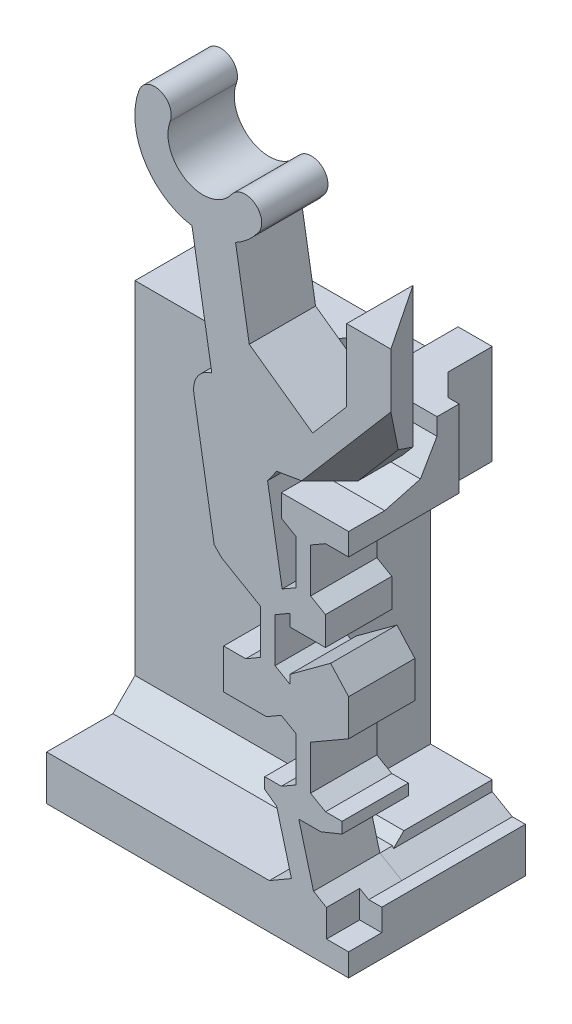
SolidWorks part; units mm, degrees
material "Nylon 6/12"
ref_plane "Front Plane" through (0, 0, 0) normal (0, 0, 1) x (1, 0, 0)
ref_plane "Top Plane" through (0, 0, 0) normal (0, 1, 0) x (1, 0, 0)
ref_plane "Right Plane" through (0, 0, 0) normal (1, 0, 0) x (0, 0, -1)
sketch "Sketch-SkeletonConfigUp" plane through (0, 0, 0) normal (0, 0, 1) x (1, 0, 0)
  line L0 (0, 0) -> (0, -50000) construction
  line L1 (0, 0) -> (4.5811, 6.2164) construction
  line L2 (9.8143, 13.3177) -> (4.5811, 13.945) construction
  line L3 (4.5811, 13.945) -> (2.9713, 10.4094) construction
  line L4 (2.9713, 10.4094) -> (4.5811, 6.2164) construction
  line L5 (4.5811, 13.945) -> (6.2429, 19.1409) construction
  line L6 (2.9713, 10.4094) -> (0.0405, 27.8193) construction
  line L7 (4.5811, 6.2164) -> (9.8143, 13.3177) construction
  line L8 (-587.3593, -797.0242) -> (9.8143, 13.3177) construction
  dimension "D2" = 7.7221
  dimension "D3" = 8.8212
  dimension "D4" = 5.2707
  dimension "D5" = 119.553
  dimension "D6" = 3.8848
  dimension "D7" = 5.4552
  dimension "D8" = 17.6549
  dimension "D9" = 4.4914
  dimension "D10" = 6.745
  dimension "D11" = 145.964
  dimension "D12" = 143.612
sketch "Sketch-SkeletonConfigDown" plane through (0, 0, 0) normal (0, 0, 1) x (1, 0, 0)
  line L0 (0, 0) -> (0, -50000) construction
  line L1 (0, 0) -> (4.5811, 6.2164) construction
  line L2 (9.8143, 13.3177) -> (4.5811, 13.945) construction
  line L3 (4.5811, 13.945) -> (6.1909, 10.4094) construction
  line L4 (6.1909, 10.4094) -> (4.5811, 6.2164) construction
  line L5 (4.5811, 13.945) -> (1.753, 18.6098) construction
  line L6 (6.1909, 10.4094) -> (-8.8652, 19.6294) construction
  line L7 (4.5811, 6.2164) -> (9.8143, 13.3177) construction
  line L8 (-589.9357, -800.5203) -> (9.8143, 13.3177) construction
  dimension "D2" = 7.7221
  dimension "D3" = 8.8212
  dimension "D4" = 5.2707
  dimension "D5" = 119.553
  dimension "D6" = 3.8848
  dimension "D7" = 5.4552
  dimension "D8" = 17.6549
  dimension "D9" = 4.4914
  dimension "D10" = 6.745
  dimension "D11" = 145.964
  dimension "D1" = 143.612
ref_plane "Plane-Cam Base" through (9.128, 0, 0) normal (1, 0, 0) x (0, 0, -1)
ref_plane "Plane-Down-to-Up Derailleur Clearance" through (6.628, 0, 0) normal (1, 0, 0) x (0, 0, -1)
ref_plane "Plane-Cam Cavity Roof" through (5.128, 0, 0) normal (1, 0, 0) x (0, 0, -1)
sketch "Sketch-SwitchBossUp" plane through (0, 0, 0) normal (0, 0, 1) x (1, 0, 0)
  line L0 (3.5811, 11.4759) -> (3.5811, 12.945) construction
  line L2 (6.5405, 21.1774) -> (6.5405, 24.4384)
  line L3 (6.5405, 24.4384) -> (8.5405, 24.4384)
  line L4 (8.5405, 24.4384) -> (8.5405, 20.4384)
  line L5 (5.5811, 12.5552) -> (5.5811, 11.263)
  line L7 (1.5115, 25.1048) -> (2.5464, 18.9575)
  line L8 (-0.4607, 24.7728) -> (0.4359, 19.4465)
  line L9 (2.9713, 10.4094) -> (0.0405, 27.8193) construction
  line L11 (-0.0396, 22.2712) -> (1.9326, 22.6032) construction
  line L15 (6.628, -23.7286) -> (6.628, 23.7286) construction
  line L16 (2.9713, 10.4094) -> (4.5811, 6.2164) construction
  line L17 (3.5811, 12.945) -> (3.5811, 14.945) construction
  line L18 (5.5811, 12.945) -> (5.5811, 14.945) construction
  line L19 (4.2561, 13.945) -> (4.9061, 13.945) construction
  line L20 (3.5811, 14.945) -> (5.5811, 14.945) construction
  line L21 (3.5811, 12.945) -> (5.5811, 12.945) construction
  line L22 (4.5811, 12.945) -> (4.5811, 14.945) construction
  line L23 (4.5811, 6.2164) -> (8.5405, 7.1023) construction
  line L24 (1.9713, 9.4094) -> (1.9713, 11.4094) construction
  line L25 (3.9713, 9.4094) -> (3.9713, 11.4094) construction
  line L26 (3.9713, 9.4094) -> (1.9713, 9.4094) construction
  line L27 (1.9713, 11.4094) -> (3.9713, 11.4094) construction
  line L28 (3.5811, 7.2164) -> (5.5811, 7.2164) construction
  line L29 (3.5811, 7.2164) -> (3.5811, 5.2164) construction
  line L30 (5.5811, 7.2164) -> (5.5811, 5.2164) construction
  line L31 (3.5811, 5.2164) -> (5.5811, 5.2164) construction
  line L32 (4.9061, 6.2164) -> (4.2561, 6.2164) construction
  line L40 (3.2963, 10.4094) -> (2.6463, 10.4094) construction
  line L43 (2.874, 4.5093) -> (0.7934, 4.5093) construction
  line L51 (4.9929, 19.3693) -> (2.5464, 18.9575)
  line L66 (0.0405, 27.8193) -> (0.0405, 50027.8193) construction
  line L74 (0.5455, 12.7717) -> (-0.3728, 18.2264)
  line L75 (0.3841, 13.7302) -> (2.3564, 14.0622) construction
  line L76 (5.5811, 11.263) -> (5.5811, 12.5552) construction
  line L77 (5.5811, 7.6061) -> (6.628, 8.2105)
  line L80 (5.8152, 10.763) -> (6.628, 9.8603)
  line L81 (8.5405, 1033.6218) -> (8.5405, 20.4384) construction
  line L82 (2.5464, 18.9575) -> (3.5585, 12.945) construction
  line L83 (3.6203, 12.5779) -> (2.8784, 16.9852)
  line L84 (2.8784, 16.9852) -> (6.0405, 17.5175)
  line L85 (6.9307, 9.5241) -> (8.5405, 7.7363) construction
  line L88 (3.5811, 16.3347) -> (6.8573, 16.3347)
  line L92 (3.7762, 8.3129) -> (6.9307, 9.5241) construction
  line L93 (6.3311, 4.3267) -> (5.3731, 3.937)
  line L95 (2.5464, 18.9575) -> (2.8784, 16.9852) construction
  line L96 (2.7124, 17.9713) -> (8.5405, 18.9524) construction
  line L97 (2.7124, 17.9713) -> (1.7262, 17.8053) construction
  line L98 (1.9713, 9.0197) -> (0.9713, 9.0197)
  line L99 (0.9713, 9.0197) -> (0.9713, 7.2164)
  line L100 (0.9713, 7.2164) -> (2.9061, 7.2164)
  line L101 (4.5811, 6.2164) -> (6.9307, 9.5241) construction
  line L103 (0.0405, 27.8193) -> (1.9448, 26.4638) construction
  line L104 (6.9307, 9.5241) -> (8.5405, 7.7363) construction
  line L106 (13.4511, 14.945) -> (5.5811, 14.945) construction
  line L107 (1.9713, 9.4094) -> (1.9713, 9.0197) construction
  line L109 (0.0405, 27.8193) -> (-2.1498, 28.6358) construction
  line L110 (8.5405, 20.4384) -> (6.0405, 17.5175)
  line L111 (6.628, 9.8603) -> (6.628, 8.2105)
  line L112 (6.628, 9.8603) -> (6.9307, 9.5241) construction
  line L113 (2.8311, 4.8267) -> (2.8311, 4.3267)
  line L114 (7.3693, 7.7363) -> (7.3563, 7.7363) construction
  line L115 (6.8573, 16.3347) -> (13.4511, 16.3347)
  line L116 (13.4511, 16.3347) -> (13.4511, -1.1653)
  line L117 (13.4511, -1.1653) -> (5.0405, -1.1653)
  line L119 (10.4375, 14.0252) -> (10.4375, 2.1692)
  line L121 (5.0405, -1.1653) -> (5.0405, 1.4417) construction
  line L122 (8.237, 12.8031) -> (10.844, 12.8031) construction
  line L123 (10.844, 12.8031) -> (13.4511, 12.8031) construction
  line L124 (10.4375, 2.1692) -> (9.128, 0.8597)
  line L125 (8.5405, 7.5847) -> (13.4511, 7.5847) construction
  line L127 (5.5811, 15.3347) -> (5.5811, 14.945) construction
  line L130 (6.0377, 0.8597) -> (9.128, 0.8597)
  line L132 (2.8311, 4.3267) -> (3.3706, 3.937)
  line L133 (2.9713, 10.4094) -> (6.1909, 10.4094) construction
  line L134 (4.5811, 10.4094) -> (4.5811, 13.945) construction
  line L135 (4.5811, 10.4094) -> (4.5811, 6.2164) construction
  line L136 (0.8973, 12.4192) -> (0.5455, 12.7717)
  line L137 (3.9713, 9.4094) -> (5.5811, 7.2164) construction
  line L139 (5.8152, 10.763) -> (3.9713, 9.4094)
  line L141 (4.0405, 1.437) -> (3.0405, 0.8597)
  line L142 (3.0405, 0.8597) -> (3.0405, -1.1653)
  line L143 (8.5405, 20.4384) -> (8.5405, 18.9524) construction
  line L145 (8.5405, 17.9384) -> (8.5405, -49992.0368) construction
  line L147 (5.5811, 11.263) -> (5.5811, 12.5552) construction
  line L149 (6.3311, 4.8267) -> (6.3311, 4.3267)
  line L150 (3.0405, -1.1653) -> (5.0405, -1.1653)
  line L151 (3.3706, 3.937) -> (5.3731, 3.937) construction
  line L152 (4.2561, 14.945) -> (4.2561, 12.945)
  line L153 (4.9061, 14.945) -> (4.9061, 12.945)
  line L155 (4.2561, 14.945) -> (3.5811, 15.3347)
  line L156 (4.9061, 14.945) -> (5.5811, 15.3347)
  line L157 (3.5811, 16.3347) -> (3.5811, 15.3347)
  line L158 (5.5811, 15.3347) -> (9.128, 15.3347)
  line L162 (3.2963, 11.4094) -> (3.2963, 9.4094)
  line L164 (2.6463, 11.4094) -> (2.6463, 9.4094)
  line L169 (4.2561, 7.2164) -> (4.2561, 5.2164)
  line L170 (4.9061, 5.2164) -> (4.9061, 7.2164)
  line L175 (4.2561, 7.2164) -> (3.5811, 7.6061)
  line L176 (4.9061, 7.2164) -> (5.5811, 7.6061)
  line L177 (5.5811, 7.2164) -> (5.5811, 7.6061) construction
  line L179 (4.2561, 5.2164) -> (3.5811, 4.8267)
  line L180 (3.5811, 5.2164) -> (3.5811, 4.8267) construction
  line L181 (3.5811, 4.8267) -> (2.8311, 4.8267)
  line L183 (4.9061, 5.2164) -> (5.5811, 4.8267)
  line L184 (5.5811, 5.2164) -> (5.5811, 4.8267) construction
  line L186 (9.128, -23.7286) -> (9.128, 23.7286) construction
  line L187 (2.6463, 9.4094) -> (1.9713, 9.0197)
  line L188 (3.2963, 9.4094) -> (3.9713, 9.0197)
  line L189 (3.2963, 11.4094) -> (3.9713, 11.7991)
  line L190 (2.6463, 11.4094) -> (0.8973, 12.4192)
  line L191 (3.9713, 11.4094) -> (3.9713, 11.7991) construction
  line L192 (3.9713, 11.7991) -> (3.9713, 11.263)
  line L193 (4.9061, 12.945) -> (5.5811, 12.5552)
  line L194 (4.2561, 12.945) -> (3.6203, 12.5779)
  line L195 (3.9713, 11.263) -> (5.5811, 11.263)
  line L196 (3.9713, 9.4094) -> (3.9713, 9.0197)
  line L197 (3.5811, 7.2164) -> (3.5811, 7.6061) construction
  line L199 (3.5811, 7.6061) -> (2.9061, 7.2164)
  line L200 (5.5811, 4.8267) -> (6.3311, 4.8267)
  line L201 (2.8311, 4.3267) -> (2.8311, 3.937) construction
  line L202 (2.8311, 3.937) -> (3.3706, 3.937) construction
  line L203 (10.4375, 14.0252) -> (9.128, 15.3347)
  line L204 (5.0405, 1.437) -> (3.0405, 1.437) construction
  line L205 (3.0405, 1.437) -> (3.0405, 0.8597) construction
  line L206 (5.0405, 1.4417) -> (6.0377, 0.8597)
  line L207 (8.5405, 18.9524) -> (8.5405, 17.9384) construction
  line L208 (6.0405, 17.5175) -> (8.5405, 17.9384) construction
  line L209 (8.5405, 20.4384) -> (8.5405, 17.9384) construction
  line L210 (6.5405, 21.1774) -> (4.9929, 19.3693)
  line L211 (5.0405, 1.4417) -> (4.3719, 3.937)
  line L212 (4.0405, 1.437) -> (3.3706, 3.937)
  line L213 (5.3731, 3.937) -> (4.3719, 3.937)
  arc A0 (1.5115, 25.1048) -> (2.5558, 26.0289) centre (0.0405, 27.8193) ccw
  arc A1 (-0.4607, 24.7728) -> (-2.8525, 28.8978) centre (0.0405, 27.8193) cw
  arc A2 (-2.8525, 28.8978) -> (-1.447, 28.3738) centre (-2.1498, 28.6358) cw
  arc A3 (2.5558, 26.0289) -> (1.3338, 26.8987) centre (1.9448, 26.4638) ccw
  arc A4 (-1.447, 28.3738) -> (1.3338, 26.8987) centre (0.0405, 27.8193) ccw
  arc A5 (3.5811, 12.945) -> (3.5811, 14.945) centre (3.1778, 13.945) ccw construction
  arc A6 (5.5811, 12.945) -> (5.5811, 14.945) centre (5.9843, 13.945) cw construction
  arc A7 (2.5293, 9.921) -> (1.9713, 11.4094) centre (1.568, 10.4094) ccw construction
  arc A8 (3.9713, 11.4094) -> (3.9713, 9.4094) centre (4.3745, 10.4094) ccw construction
  arc A9 (3.5811, 7.2164) -> (3.5811, 5.2164) centre (3.1779, 6.2164) cw construction
  arc A10 (5.5811, 7.2164) -> (5.5811, 5.2164) centre (5.9844, 6.2164) ccw construction
  arc A19 (-0.3728, 18.2264) -> (0.4359, 19.4465) centre (0.6836, 18.4042) cw
  circle A28 centre (0.0405, 27.8193) radius 2.3375 construction
  arc A29 (1.9713, 9.4094) -> (2.5293, 9.921) centre (1.568, 10.4094) ccw construction
  point P53 (4.5811, 13.945)
  point P63 (2.9713, 10.4094)
  point P73 (3.3627, 3.937)
  point P93 (0.9465, 22.4372)
  dimension "D23" = 1.5875
  dimension "D24" = 0.75
  dimension "D2" = 2
  dimension "D5" = 2
  dimension "D6" = 0.65
  dimension "D8" = 42
  dimension "D7" = 2
  dimension "D11" = 8.5
  dimension "D14" = 7.5
  dimension "D4" = 3
  dimension "D16" = 42
  dimension "D25" = 120
  dimension "D26" = 120
  dimension "D27" = 120
  dimension "D28" = 120
  dimension "D29" = 120
  dimension "D30" = 120
  dimension "D31" = 120
  dimension "D32" = 120
  dimension "D33" = 120
  dimension "D34" = 120
  dimension "D35" = 120
  dimension "D36" = 120
  dimension "D17" = 0.5
  dimension "D20" = 3.5
  dimension "D21" = 1
  dimension "D18" = 45
  dimension "D9" = 17.5
  dimension "D22" = 1
  dimension "D15" = 45
  dimension "D38" = 2
  dimension "D39" = 0.5
  dimension "D40" = 60
  dimension "D41" = 1
  dimension "D42" = 45
  dimension "D43" = 120
  dimension "D44" = 2
  dimension "D45" = 2.5
  dimension "D46" = 2.5
  dimension "D47" = 4
  dimension "D48" = 2
  dimension "D10" = 15
  dimension "D12" = 2.5
  dimension "D13" = 1
extrude "Boss-Switch Main" add sketch "Sketch-SwitchBossUp" along normal blind 3
sketch "Sketch1" plane through (0, 0, 0) normal (0, 0, -1) x (-1, 0, 0)
  line L0 (-3.5811, 16.3347) -> (-3.5811, 15.3347) construction
  line L1 (-7.5811, -1.1653) -> (0.4122, -1.1653)
  line L2 (-7.5811, -1.1653) -> (-7.5811, 0.8597)
  line L4 (0.4122, -1.1653) -> (0.4122, 0.8597)
  line L5 (-3.5811, 18.8347) -> (-7.5811, 18.8347)
  line L10 (-7.5811, 18.8347) -> (-7.5811, 15.3347)
  line L11 (-4.0405, 1.437) -> (-5.0417, 1.437)
  line L12 (-7.5811, 15.3347) -> (-3.5811, 15.3347)
  line L13 (-4.0405, 1.437) -> (-3.0405, 0.8597)
  line L14 (-3.5811, 15.3347) -> (-3.5811, 18.8347)
  line L20 (-4.3719, 3.937) -> (-5.0405, 1.4417) construction
  line L22 (-3.0405, -1.1653) -> (-13.4511, -1.1653) construction
  line L23 (-3.0405, 0.8597) -> (0.4122, 0.8597)
  line L24 (-5.0417, 1.437) -> (-6.0377, 0.8597)
  line L25 (-6.0377, 0.8597) -> (-7.5811, 0.8597)
  line L26 (-9.128, 15.3347) -> (-5.5811, 15.3347) construction
  point P8 (0, 0)
  point P11 (0, 0)
  point P18 (0, 0)
  point P19 (-4.0405, 1.437)
  point P21 (-5.0405, 1.4417)
  dimension "D1" = 3.5
  dimension "D4" = 4
extrude "Boss-Flange Width" add sketch "Sketch1" along normal blind 5
ref_plane "Plane-Sta2Sit Groove" through (0.0405, 0, 0) normal (1, 0, 0) x (0, 0, -1)
ref_plane "Plane-Cam Outer Surface" through (-12.0395, 0, 0) normal (1, 0, 0) x (0, 0, -1)
ref_plane "Plane-FlangeTop" through (-7.0395, 0, 0) normal (1, 0, 0) x (0, 0, -1)
sketch "Sketch2" plane through (-7.0395, 0, 0) normal (1, 0, 0) x (0, 0, -1)
  line L0 (5, 15.3347) -> (0, 15.3347) construction
  line L1 (5, 17.3347) -> (1, 17.3347)
  line L2 (5, 17.3347) -> (5, 15.3347)
  line L3 (5, 15.3347) -> (1, 15.3347)
  line L4 (1, 17.3347) -> (1, 15.3347)
  line L10 (-3, -1.1653) -> (-3, 16.3347) construction
  line L11 (5, 0.8597) -> (-3, 0.8597)
  line L12 (5, 0.8597) -> (5, -1.1653)
  line L13 (5, -1.1653) -> (-3, -1.1653)
  line L14 (-3, 0.8597) -> (-3, -1.1653)
  line L15 (0, 10.4094) -> (0, 27.8193) construction
  line L17 (5, 0.8597) -> (5, -1.1653) construction
  line L18 (-3, 0.8597) -> (0, 0.8597) construction
  dimension "D1" = 1
  dimension "D2" = 2
extrude "Boss-Flange Height" add sketch "Sketch2" along normal up to surface (11.6675 mm away)
sketch "Sketch10" plane through (0, 15.3347, 0) normal (0, 1, 0) x (1, 0, 0)
  line L0 (9.128, -23.7286) -> (9.128, 23.7286) construction
  line L1 (7.5811, 5) -> (5.128, 5)
  line L2 (7.5811, 5) -> (7.5811, 2)
  line L3 (7.5811, 2) -> (5.128, 2)
  line L5 (4.628, 7) -> (4.628, 1) construction
  line L6 (3.5811, 1) -> (-7.0395, 1) construction
  line L8 (5.128, 5) -> (5.128, 2)
  dimension "D1" = 1
  dimension "D2" = 0.5
  dimension "D3" = 4.5
extrude "Cut-Up-To-Down Derailleur Clearance" cut sketch "Sketch10" along normal up to next
sketch "Sketch17" plane through (0, 15.3347, 0) normal (0, -1, 0) x (1, 0, 0)
  line L0 (5.128, -5) -> (-7.0395, -5)
  line L1 (5.128, -5) -> (3.5811, -5) construction
  line L2 (-7.0395, -5) -> (-7.0395, -1)
  line L3 (-7.0395, -1) -> (5.128, -1)
  line L4 (5.128, -1) -> (5.128, -5)
  line L5 (-7.0395, -1) -> (-7.0395, -5) construction
extrude "Boss-Flange Support" add sketch "Sketch17" along normal up to surface (14.475 mm away) up to face at (-1.9995, 0.8597, -1)
sketch "Sketch-HolePositions" plane through (0, -1.1653, 0) normal (0, -1, 0) x (1, 0, 0)
  line L0 (-7.0395, -3) -> (7.5811, -3) construction
  line L1 (7.5811, -5) -> (-7.0395, -5) construction
  line L2 (7.5811, -5) -> (7.5811, 0) construction
  line L4 (-7.0395, -22.2167) -> (-7.0395, 22.2167) construction
  line L5 (3.5811, -1) -> (3.5811, -5) construction
  point P6 (-4.0395, -3)
  point P7 (0.5811, -3)
  dimension "D1" = 3
  dimension "D2" = 3
  dimension "D3" = 2
sketch "Sketch6" plane through (0, -1.1653, 0) normal (0, -1, 0) x (-1, 0, 0)
  point P0 (4.0395, 3)
  point P3 (-0.5811, 3)
hole_wizard "Tap Drill for M2x0.4 Tap1" positions "Sketch6" profile "Sketch5" hole size "M2x0.4" standard "ANSI Metric" end condition through all
sketch "Sketch5" plane through (-4.0395, -1.1653, -3) normal (1, 0, 0) x (0, 0, -1)
  line L0 (0, 0) -> (0, 30.5511)
  line L1 (0, 30.5511) -> (0.8, 30.5511)
  line L2 (0.8, 30.5511) -> (0.8, 0)
  line L5 (0.8, 0) -> (0, 0)
  line L11 (0, -6.35) -> (0, 107.95) construction
  dimension "Thru Hole Dia." = 1.6
  dimension "Thru Hole Depth" = 30.5511
sketch "Sketch9" plane through (0, -1.1653, 0) normal (0, -1, 0) x (1, 0, 0)
  point P0 (-4.0395, -3)
  point P3 (0.5811, -3)
hole_wizard "M2 Clearance Hole2" positions "Sketch9" profile "Sketch8" hole size "M2" standard "ANSI Metric"
sketch "Sketch8" plane through (-4.0395, -1.1653, -3) normal (1, 0, 0) x (0, 0, -1)
  line L0 (0, 0) -> (0, 15.721)
  line L1 (0, 15.721) -> (1.2, 15)
  line L2 (1.2, 15) -> (1.2, 0)
  line L5 (1.2, 0) -> (0, 0)
  line L10 (0, 15.721) -> (-1.2, 15) construction
  line L11 (0, -6.35) -> (0, 107.95) construction
  dimension "Hole Dia." = 2.4
  dimension "Hole Depth" = 15
  dimension "Drill Angle" = 118
sketch "Sketch-Measurements for Derailleur Ramps" plane through (0, 0, 0) normal (0, 0, 1) x (1, 0, 0)
  line L0 (2.8784, 16.9852) -> (2.5464, 18.9575)
  line L1 (2.7124, 17.9713) -> (1.7262, 17.8053)
  line L2 (2.9713, 10.4094) -> (0.0405, 27.8193) construction
  line L3 (1.7262, 17.8053) -> (-1.8937, 15.3603)
  line L4 (6.1909, 10.4094) -> (-8.8652, 19.6294) construction
  line L5 (1.7262, 17.8053) -> (2.6012, 12.6077)
  line L6 (2.6012, 12.6077) -> (-1.8937, 15.3603)
  line L7 (-0.0837, 16.5828) -> (-0.0837, 17.8053)
  line L8 (-0.0837, 17.8053) -> (1.7262, 17.8053)
  line L9 (6.1909, 10.4094) -> (2.9713, 10.4094)
  line L10 (5.386, 8.3129) -> (3.7762, 8.3129)
  line L12 (6.1909, 10.4094) -> (4.5811, 6.2164) construction
  line L13 (4.5811, 8.3129) -> (4.5811, 8.7912)
  line L14 (4.5811, 6.2164) -> (5.386, 8.3129)
  line L15 (2.9713, 10.4094) -> (4.5811, 6.2164) construction
  line L16 (3.7762, 8.3129) -> (4.5811, 6.2164)
  line L17 (5.386, 8.3129) -> (5.386, 8.7912)
  dimension "D1" = 1.81
  dimension "D2" = 0.8049
sketch "Sketch12" plane through (0, 24.4384, 0) normal (0, 1, 0) x (1, 0, 0)
  line L0 (6.5405, 0) -> (8.5405, -3)
  line L1 (8.5405, -3) -> (8.5405, 0)
  line L2 (8.5405, 0) -> (6.5405, 0)
extrude "Cut-Up-to-Down Cantilever Slope" cut sketch "Sketch12" against normal up to next
ref_plane "Plane1" through (0, 7.1023, 0) normal (0, 1, 0) x (1, 0, 0)
sketch "Sketch-Derailleur Location" plane through (0, 7.1023, 0) normal (0, 1, 0) x (1, 0, 0)
  line L0 (8.5405, 0) -> (8.5405, -3)
  line L1 (4.0405, -3) -> (3.0405, -3) construction
  line L2 (-119237.4187, 0) -> (9.8143, 0) construction
  point P0 (8.5405, 0)
  point P8 (8.5405, -1.5)
ref_plane "Plane-Cantilever Cut" [suppressed] through (7.0848, 8.5204, -1.9058) normal (-0.6301, -0.7578, 0.1695) x (-0.7765, 0.6151, -0.1368)
sketch "Sketch14" [suppressed] plane through (7.0848, 8.5204, -1.9058) normal (-0.6301, -0.7578, 0.1695) x (-0.7765, 0.6151, -0.1368)
  line L0 (2.3023, -1.6911) -> (-0.3551, -1.6911)
  line L2 (2.3023, -4.3362) -> (2.3023, -1.6911)
  line L3 (-0.3551, -1.6911) -> (-0.3551, -4.4608)
  line L5 (-0.3551, -4.4608) -> (1.0087, -5.0843)
  line L6 (1.0087, -5.0843) -> (2.3023, -4.3362)
extrude "Cut-Down-to-Up Cantilever Slope" [suppressed] cut sketch "Sketch14" against normal up to next
sketch "Sketch16" plane through (0, 0, 0) normal (0, 0, -1) x (-1, 0, 0)
  line L0 (-7.5811, 18.8347) -> (-13.4511, 18.8347)
  line L1 (-13.4511, 18.8347) -> (-13.4511, -1.1653)
  line L2 (-13.4511, -1.1653) -> (-6.628, -1.1653)
  line L3 (-13.4511, -1.1653) -> (-5.0405, -1.1653) construction
  line L4 (-6.628, -1.1653) -> (-6.628, 5.2038)
  line L5 (-6.628, 5.2038) -> (-8.0037, 5.2038)
  line L6 (-8.0037, 5.2038) -> (-8.0037, 12.0484)
  line L7 (-8.0037, 12.0484) -> (-6.628, 12.0484)
  line L8 (-6.628, 12.0484) -> (-6.628, 17.9477)
  line L9 (-6.628, 23.7286) -> (-6.628, -23.7286) construction
  line L10 (-3.5811, 18.8347) -> (-6.5405, 18.8347) construction
  line L11 (-7.5811, 18.8347) -> (-6.628, 17.9477)
extrude "Cut-Down-to-Up Derailleur Clearance" cut sketch "Sketch16" against normal through all and the other way through all
ref_plane "Plane-Symmetry Plane" through (0, 0, 1.5) normal (0, 0, 1) x (1, 0, 0)
sketch "Sketch-Cable Center Point"
  dimension "D1" = 0.7937
chamfer "Chamfer-Flange Support" distance 1.5 angle 45 1 edges at (3.5811, 17.3347, -3)
chamfer "Chamfer-Flange Support 2" distance 1 angle 45 2 edges at (5.128, 17.0847, -2) (5.128, 15.3347, -1.5)
chamfer "Chamfer-Flange Support 3" distance 1 angle 45 1 edges at (-1.9995, 0.8597, -1)
sketch "Sketch18" plane through (6.628, 0, 0) normal (1, 0, 0) x (0, 0, -1)
  line L1 (-3, -0.1403) -> (-1.5, -0.1403)
  line L2 (-3, -0.1403) -> (-3, 1.437)
  line L3 (-3, 1.437) -> (-1.5, 1.437)
  line L4 (-1.5, -0.1403) -> (-1.5, 1.437)
  line L5 (0.5774, 1.437) -> (0, 1.437) construction
  line L6 (-3, -1.1653) -> (-3, 0.8597) construction
  line L7 (-3, 0.8597) -> (0, 0.8597) construction
  dimension "D1" = 1.5
  dimension "D2" = 1
extrude "Cut-Down-to-Up Derailleur Clearance 2" cut sketch "Sketch18" against normal blind 1
sketch "Sketch19" plane through (0, 0, 0) normal (0, 0, 1) x (1, 0, 0)
  line L7 (3.5811, 18.8347) -> (6.628, 18.8347)
  line L8 (6.628, 18.8347) -> (6.628, 16.3347)
  line L9 (6.628, 16.3347) -> (3.5811, 16.3347)
  line L10 (3.5811, 16.3347) -> (3.5811, 18.8347)
  line L11 (6.628, 16.3347) -> (6.628, 17.9477) construction
extrude "Cut-Up-to-Down Cantilever Clearance" cut sketch "Sketch19" against normal up to surface (1 mm away) up to face at (1.4435, 12.7784, -1)
chamfer "Chamfer1" distance 1 angle 60 1 edges at (5.1045, 16.3347, -1) first distance on face at (5.1045, 16.3347, 1)
chamfer "Chamfer3" distance 0.75 angle 60 1 edges at (3.5811, 16.7007, -1) first distance on face at (3.5811, 16.1233, 0.6667)
chamfer "Chamfer4" distance 0.5 angle 60 1 edges at (4.205, 15.3347, -1) first distance on face at (5.1242, 15.3347, -0.0278)
chamfer "Chamfer5" distance 0.5 angle 45 1 edges at (2.8784, 16.9852, 1.5)
chamfer "Chamfer6" distance 2.5 angle 45 1 edges at (2.5464, 18.9575, 1.5)
chamfer "Chamfer7" distance 1 angle 45 1 edges at (7.2905, 18.978, 3)
sketch "Sketch22" plane through (0, 0, 0) normal (0, 0, 1) x (1, 0, 0)
  line L0 (6.628, 17.9477) -> (7.5811, 18.8347) construction
  line L1 (6.628, 18.8347) -> (7.5811, 18.8347) construction
  line L2 (6.628, 17.9477) -> (6.628, 18.8347) construction
  line L3 (6.628, 17.9477) -> (7.5811, 18.8347)
  line L4 (6.628, 18.8347) -> (7.5811, 18.8347)
  line L5 (6.628, 17.9477) -> (6.628, 18.8347)
extrude "Cut-Extrude3" cut sketch "Sketch22" against normal up to next
chamfer "Chamfer8" distance 0.5 angle 45 1 edges at (5.1045, 16.3347, 0) first distance on face at (4.2965, 17.2286, -0.5161)
sketch "Sketch23" plane through (0, 0, -1) normal (0, 0, 1) x (1, 0, 0)
  line L0 (5.128, 1.8597) -> (2.3369, 1.8597)
  line L1 (-7.0395, 1.8597) -> (5.128, 1.8597) construction
  line L2 (2.3369, 1.8597) -> (2.3369, 14.3347)
  line L3 (2.3369, 14.3347) -> (5.128, 14.3347)
  line L4 (5.128, 14.3347) -> (5.128, 1.8597)
extrude "Cut-Extrude4" cut sketch "Sketch23" against normal through all
equation "\"axle-diameter\"=2"
equation "\"switch-thickness\"=12"
equation "\"base-width\"=4.0"
equation "\"axle-bushing-radius\"=3"
equation "\"clearance\"= 0.25"
equation "\"arm-width\"=1.5"
equation "\"min-diameter\"=70"
equation "\"alpha\"=143.6120"
equation "\"gamma\"=119.5526"
equation "\"delta\"=145.9637"
equation "\"epsilon\"=6.7452"
equation "\"l_AB\"=8.8212"
equation "\"l_AC\"=4.4914"
equation "\"l_BD\"=5.2707"
equation "\"l_CD\"=3.8848"
equation "\"l_CE\"=17.6549"
equation "\"l_DF\"=5.4552"
equation "\"l_OA\"=7.7221"
equation "\"D2@Sketch-SkeletonConfigUp\" = \"l_OA\""
equation "\"D3@Sketch-SkeletonConfigUp\" = \"l_AB\""
equation "\"D4@Sketch-SkeletonConfigUp\" = \"l_BD\""
equation "\"D5@Sketch-SkeletonConfigUp\" = \"gamma\""
equation "\"D6@Sketch-SkeletonConfigUp\" = \"l_CD\""
equation "\"D7@Sketch-SkeletonConfigUp\" = \"l_DF\""
equation "\"D8@Sketch-SkeletonConfigUp\" = \"l_CE\""
equation "\"D9@Sketch-SkeletonConfigUp\" = \"l_AC\""
equation "\"D_groove\"=3.175"
equation "\"D7@Sketch-SkeletonConfigDown\" = \"l_DF\""
equation "\"D6@Sketch-SkeletonConfigDown\" = \"l_CD\""
equation "\"D2@Sketch-SkeletonConfigDown\" = \"l_OA\""
equation "\"D3@Sketch-SkeletonConfigDown\" = \"l_AB\""
equation "\"D9@Sketch-SkeletonConfigDown\" = \"l_AC\""
equation "\"D8@Sketch-SkeletonConfigDown\" = \"l_CE\""
equation "\"D5@Sketch-SkeletonConfigDown\" = \"gamma\""
equation "\"D4@Sketch-SkeletonConfigDown\" = \"l_BD\""
equation "\"D1@Sketch-SkeletonConfigDown\" = \"alpha\""
equation "\"hinge_length\"=1.5"
equation "\"hinge_depth\"=0.25"
equation "\"D10@Sketch-SkeletonConfigUp\"=\"epsilon\""
equation "\"D11@Sketch-SkeletonConfigUp\"=\"delta\""
equation "\"D12@Sketch-SkeletonConfigUp\"=\"alpha\""
equation "\"D11@Sketch-SkeletonConfigDown\"=\"delta\""
equation "\"D10@Sketch-SkeletonConfigDown\"=\"epsilon\""
equation "\"EE_dx\"=8.9056"
equation "\"EE_dy\"=8.1898"
equation "\"r_groove\"=\"D_groove\"/2"
equation "\"t_wall\"=25.4/16"
equation "\"width_lower\"=\"D_groove\"+\"t_wall\""
equation "\"cable_to_bottom\"=30.6257"
equation "\"switch_EE-up_base_dy\"=24"
equation "\"switch_EE-down_base_dy\"=16"
equation "\"D_axle\"=25.4/8"
equation "\"D_up_to_down\"=16"
equation "\"D_down_to_up\"=25"
equation "\"t_cam_base\"=7.5"
equation "\"D23@Sketch-SwitchBossUp\"=\"D_groove\"/2"
equation "\"D1@Sketch-Cable Center Point\"=\"D_groove\"/4"
